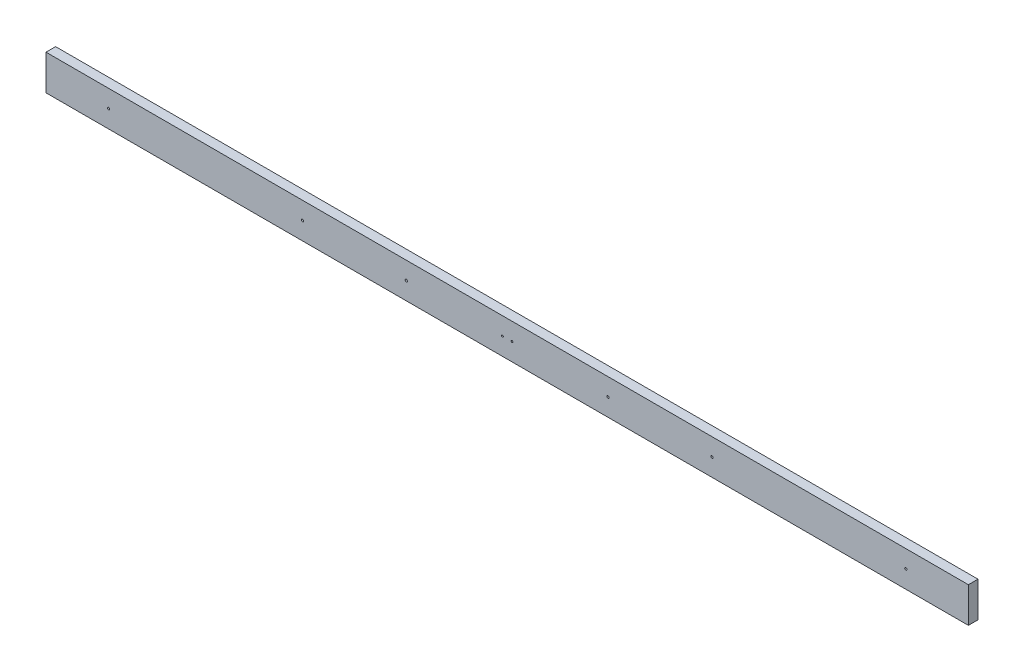
SolidWorks part; units mm, degrees
ref_plane "Front Plane" through (0, 0, 0) normal (0, 0, 1) x (1, 0, 0)
ref_plane "Top Plane" through (0, 0, 0) normal (0, 1, 0) x (1, 0, 0)
ref_plane "Right Plane" through (0, 0, 0) normal (1, 0, 0) x (0, 0, -1)
sketch "Sketch1" plane through (0, 0, 0) normal (0, 0, 1) x (1, 0, 0)
  line L1 (-1828.8, -69.85) -> (1828.8, -69.85)
  line L2 (-1828.8, -69.85) -> (-1828.8, 69.85)
  line L3 (-1828.8, 69.85) -> (1828.8, 69.85)
  line L4 (1828.8, -69.85) -> (1828.8, 69.85)
  line L5 (-1828.8, -69.85) -> (1828.8, 69.85) construction
  line L6 (-1828.8, 69.85) -> (1828.8, -69.85) construction
  point P0 (0, 0)
  dimension "D1" = 3657.6
  dimension "D2" = 139.7
extrude "Boss-Extrude1" add sketch "Sketch1" along normal blind 38.1
sketch "Sketch3" plane through (0, 0, 38.1) normal (0, 0, 1) x (1, 0, 0)
  line L0 (0, -69.85) -> (0, 69.85) construction
  line L1 (-1828.8, -69.85) -> (1828.8, -69.85) construction
  line L2 (1828.8, 69.85) -> (-1828.8, 69.85) construction
  line L3 (-25.4, -7.9375) -> (25.4, -7.9375) construction
  line L4 (-25.4, -7.9375) -> (-25.4, 7.9375) construction
  line L5 (-25.4, 7.9375) -> (25.4, 7.9375) construction
  line L6 (25.4, -7.9375) -> (25.4, 7.9375) construction
  line L7 (-19.05, 0) -> (19.05, 0) construction
  circle A0 centre (-19.05, 0) radius 3.5719
  circle A1 centre (19.05, 0) radius 3.5719
  point P14 (-25.4, 0)
  dimension "D8" = 7.1437
  dimension "D9" = 7.1437
  dimension "D1" = 15.875
  dimension "D2" = 7.9375
  dimension "D3" = 38.1
  dimension "D4" = 6.35
  dimension "D5" = 50.8
  dimension "D10" = 7.9375
extrude "Cut-Extrude2" cut sketch "Sketch3" against normal through all contours A0 | A1
sketch "Sketch4" plane through (0, 0, 38.1) normal (0, 0, 1) x (1, 0, 0)
  line L0 (0, 589.6071) -> (0, -768.8477)
  line L1 (762, 589.6071) -> (762, -768.8477)
  line L2 (0, 0) -> (-558.8, 0)
  line L3 (-558.8, 0) -> (-558.8, 478.8836)
  point P7 (558.8, 486.0592)
  point P9 (-570.9751, 478.8836)
  dimension "D1" = 762
  dimension "D2" = 558.8
sketch "Sketch5" plane through (0, 0, 38.1) normal (0, 0, 1) x (1, 0, 0)
  line L0 (-400, 0) -> (400, 0) construction
  circle A0 centre (400, 0) radius 4.4996
  circle A1 centre (-400, 0) radius 4.4996
  point P4 (0, 0)
  dimension "D2" = 8.9992
  dimension "D3" = 8.9992
  dimension "D1" = 800
extrude "Cut-Extrude3" cut sketch "Sketch5" against normal through all
sketch "Sketch6" plane through (0, 0, 38.1) normal (0, 0, 1) x (1, 0, 0)
  line L0 (1828.8, 0) -> (-1828.8, 0) construction
  line L1 (1828.8, -69.85) -> (1828.8, 69.85) construction
  line L2 (-1828.8, 69.85) -> (-1828.8, -69.85) construction
  line L3 (0, 69.85) -> (0, -69.85) construction
  line L4 (1828.8, 69.85) -> (-1828.8, 69.85) construction
  line L6 (-789.94, -403.86) -> (789.94, -403.86) construction
  line L7 (-789.94, -403.86) -> (-789.94, 403.86) construction
  line L8 (-789.94, 403.86) -> (789.94, 403.86) construction
  line L9 (789.94, -403.86) -> (789.94, 403.86) construction
  line L10 (-789.94, -403.86) -> (789.94, 403.86) construction
  line L11 (-789.94, 403.86) -> (789.94, -403.86) construction
  circle A0 centre (811.94, 0) radius 4.4996
  circle A1 centre (1580.6608, 0) radius 4.4996
  circle A3 centre (-1580.6608, 0) radius 4.4996
  circle A4 centre (-811.94, 0) radius 4.4996
  point P15 (400, 0)
  point P21 (0, 0)
  dimension "D2" = 8.9992
  dimension "D3" = 8.9992
  dimension "D1" = 768.7208
  dimension "D4" = 1579.88
  dimension "D5" = 807.72
  dimension "D6" = 22
extrude "Cut-Extrude4" cut sketch "Sketch6" against normal through all
sketch "Sketch7" plane through (0, 0, 38.1) normal (0, 0, 1) x (1, 0, 0)
  point P0 (-811.94, 0)
  point P1 (-1580.6608, 0)
  point P3 (400, 0)
  point P5 (811.94, 0)
  point P7 (1580.6608, 0)
equation "\"actuatorDistanceFromMiddle\"=558.8"
equation "\"D2@Sketch4\"=\"actuatorDistanceFromMiddle\""
